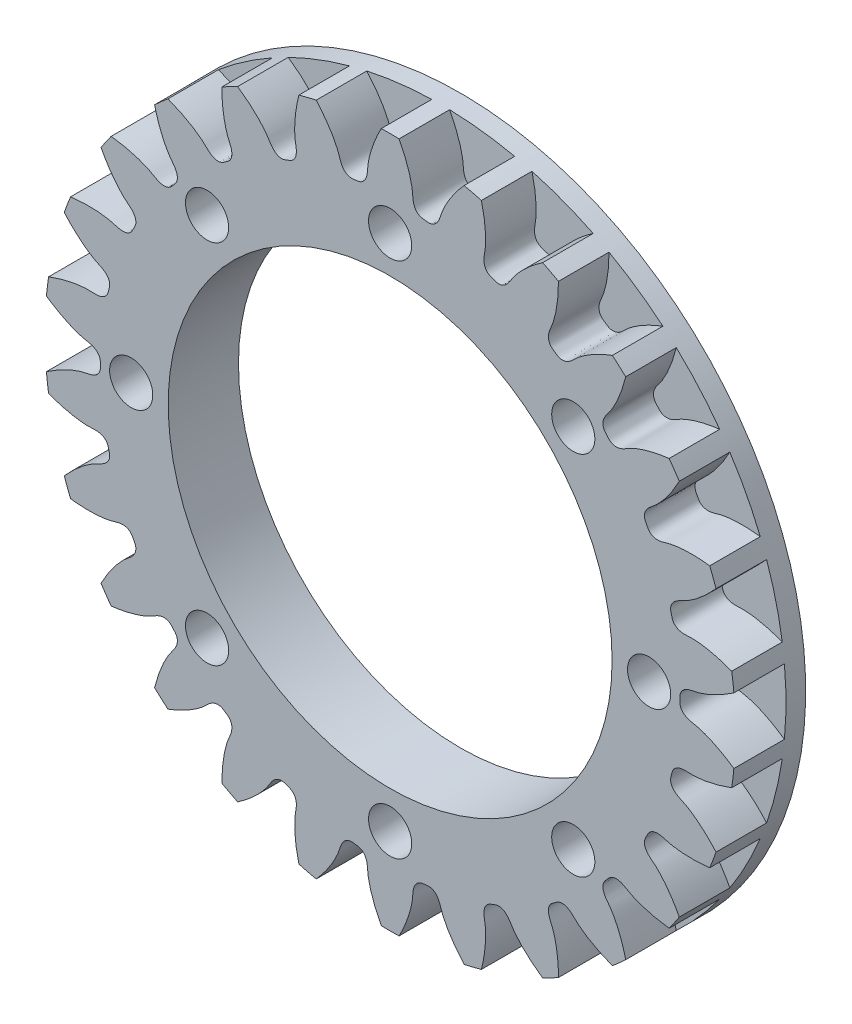
SolidWorks part; units mm, degrees
ref_plane "Front Plane" through (0, 0, 0) normal (0, 0, 1) x (1, 0, 0)
ref_plane "Top Plane" through (0, 0, 0) normal (0, 1, 0) x (1, 0, 0)
ref_plane "Right Plane" through (0, 0, 0) normal (1, 0, 0) x (0, 0, -1)
ref_axis "Axis1" through (0, 0, 55) along (0, 0, -1)
sketch "SketchRevolveSpurGear2" plane through (0, 0, 0) normal (1, 0, 0) x (0, 0, -1)
  line L0 (0, 0) -> (1, 0) construction
  line L1 (-2.1, 0) -> (-2.1, 28)
  line L2 (-2.1, 28) -> (2.1, 28)
  line L3 (2.1, 28) -> (2.1, 0)
  line L4 (2.1, 0) -> (-2.1, 0)
  dimension "Side1" = 2.1
  dimension "OutsideRadius" = 28
  dimension "Side2" = 2.1
revolve "SpurGear2" add sketch "SketchRevolveSpurGear2" angle 360 about L0
sketch "SketchToothSpurGear2" plane through (0, 0, 0) normal (0, 0, 1) x (1, 0, 0)
  arc A0 (27.9679, 2.7212) -> (27.9679, -2.7212) centre (0, 0) cw
  spline S0 degree 3 poles (27.9679, -2.7212) (27.7638, -2.5774) (27.4599, -2.3753) (27.0547, -2.1308) (26.7715, -1.9706) (26.5013, -1.8278) (26.2448, -1.7014) (26.0028, -1.5905) (25.7759, -1.4943) (25.5647, -1.4117) (25.3698, -1.3417) (25.1918, -1.2835) (25.0311, -1.2359) (24.8881, -1.198) (24.7634, -1.1686) (24.5695, -1.129) (24.3796, -1.0998) (24.1971, -1.043) (24.0968, -1.0051) (23.9998, -0.9603) (23.9053, -0.9066) (23.8125, -0.8411) (23.7215, -0.7592) (23.6349, -0.6551) (23.5594, -0.5232) (23.5122, -0.373) (23.4933, -0.1948) (23.504, 0) (23.4933, 0.1948) (23.5122, 0.373) (23.5594, 0.5232) (23.6349, 0.6551) (23.7215, 0.7592) (23.8125, 0.8411) (23.9053, 0.9066) (23.9998, 0.9603) (24.0968, 1.0051) (24.1971, 1.043) (24.3796, 1.0998) (24.5695, 1.129) (24.7634, 1.1686) (24.8881, 1.198) (25.0311, 1.2359) (25.1918, 1.2835) (25.3698, 1.3417) (25.5647, 1.4117) (25.7759, 1.4943) (26.0028, 1.5905) (26.2448, 1.7014) (26.5013, 1.8278) (26.7715, 1.9706) (27.0547, 2.1308) (27.4599, 2.3753) (27.7638, 2.5774) (27.9679, 2.7212) knots 0 0 0 0 0.067679 0.098846 0.128233 0.155839 0.181663 0.205707 0.22797 0.248452 0.267152 0.284072 0.29921 0.312568 0.324145 0.33394 0.366202 0.376043 0.385676 0.395249 0.404962 0.415087 0.425975 0.438039 0.451647 0.466885 0.480344 0.5 0.519656 0.533115 0.548353 0.561961 0.574025 0.584913 0.595038 0.604751 0.614324 0.623957 0.633798 0.66606 0.675855 0.687432 0.70079 0.715928 0.732848 0.751548 0.77203 0.794293 0.818337 0.844161 0.871767 0.901154 0.932321 1 1 1 1
extrude "ToothExtrudeCutSpurGear2" cut sketch "SketchToothSpurGear2" along normal blind 2.1 and the other way blind 2
pattern_circular "PatternSpurGear2" count 26 every 13.846 about axis through (0, 0, 55) along (0, 0, -1) of "ToothExtrudeCutSpurGear2"
sketch "BoreRevolveSketch" plane through (0, 0, 0) normal (1, 0, 0) x (0, 0, -1)
  line L0 (0, 0) -> (1, 0) construction
  line L1 (-2.1, 0) -> (2.1, 0)
  line L2 (2.1, 0) -> (2.1, 18)
  line L3 (2.1, 18) -> (-2.1, 18)
  line L4 (-2.1, 18) -> (-2.1, 0)
  dimension "BoreSide1" = 2.1
  dimension "TaperSide1" = 18
  dimension "BoreSide2" = 2.1
  dimension "TaperSide2" = 18
revolve "BoreRevolveCut" cut sketch "BoreRevolveSketch" angle 360 about L0
sketch "AuxiliarySketchSpurGear2" plane through (0, 0, 0) normal (0, 0, 1) x (1, 0, 0)
  circle A0 centre (0, 0) radius 26 construction
  circle A1 centre (0, 0) radius 24.432 construction
  circle A2 centre (0, 0) radius 24.5849 construction
  circle A3 centre (0, 0) radius 28 construction
  circle A4 centre (0, 0) radius 23.5 construction
  dimension "PitchDiameter" = 52
  dimension "BaseDiameter" = 48.864
  dimension "FormDiameter" = 49.1697
  dimension "MajorDiameter" = 56
  dimension "MinorDiameter" = 47
sketch "Sketch1" plane through (0, 0, -2.1) normal (0, 0, -1) x (-1, 0, 0)
  line L0 (0, 0) -> (0, 28) construction
  circle A0 centre (0, 0) radius 28 construction
  circle A1 centre (0, 0) radius 21 construction
  circle A2 centre (0, 21) radius 1.75
  circle A3 centre (14.8492, 14.8492) radius 1.75
  circle A4 centre (21, 0) radius 1.75
  circle A5 centre (14.8492, -14.8492) radius 1.75
  circle A6 centre (0, -21) radius 1.75
  circle A7 centre (-14.8492, -14.8492) radius 1.75
  circle A8 centre (-21, 0) radius 1.75
  circle A9 centre (-14.8492, 14.8492) radius 1.75
  point P24 (0, 0)
  dimension "D1" = 42
  dimension "D2" = 3.5
  dimension "D3" = 8
extrude "Cut-Extrude1" cut sketch "Sketch1" against normal through all
sketch "Sketch2" plane through (0, 0, -2.1) normal (0, 0, -1) x (-1, 0, 0)
  circle A0 centre (14.8492, -14.8492) radius 1.75 construction
  circle A1 centre (0, -21) radius 1.75 construction
  circle A2 centre (-14.8492, -14.8492) radius 1.75 construction
  circle A3 centre (-21, 0) radius 1.75 construction
  circle A4 centre (-14.8492, 14.8492) radius 1.75 construction
  circle A5 centre (0, 21) radius 1.75 construction
  circle A6 centre (14.8492, 14.8492) radius 1.75 construction
  circle A7 centre (21, 0) radius 1.75 construction
  circle A8 centre (14.8492, -14.8492) radius 1.75
  circle A9 centre (0, -21) radius 1.75
  circle A10 centre (-14.8492, -14.8492) radius 1.75
  circle A11 centre (-21, 0) radius 1.75
  circle A12 centre (-14.8492, 14.8492) radius 1.75
  circle A13 centre (0, 21) radius 1.75
  circle A14 centre (14.8492, 14.8492) radius 1.75
  circle A15 centre (21, 0) radius 1.75
  circle A16 centre (0, 0) radius 18 construction
  circle A17 centre (0, 0) radius 18
  circle A18 centre (0, 0) radius 28
  dimension "D1" = 56
extrude "Boss-Extrude1" add sketch "Sketch2" along normal blind 1.5
